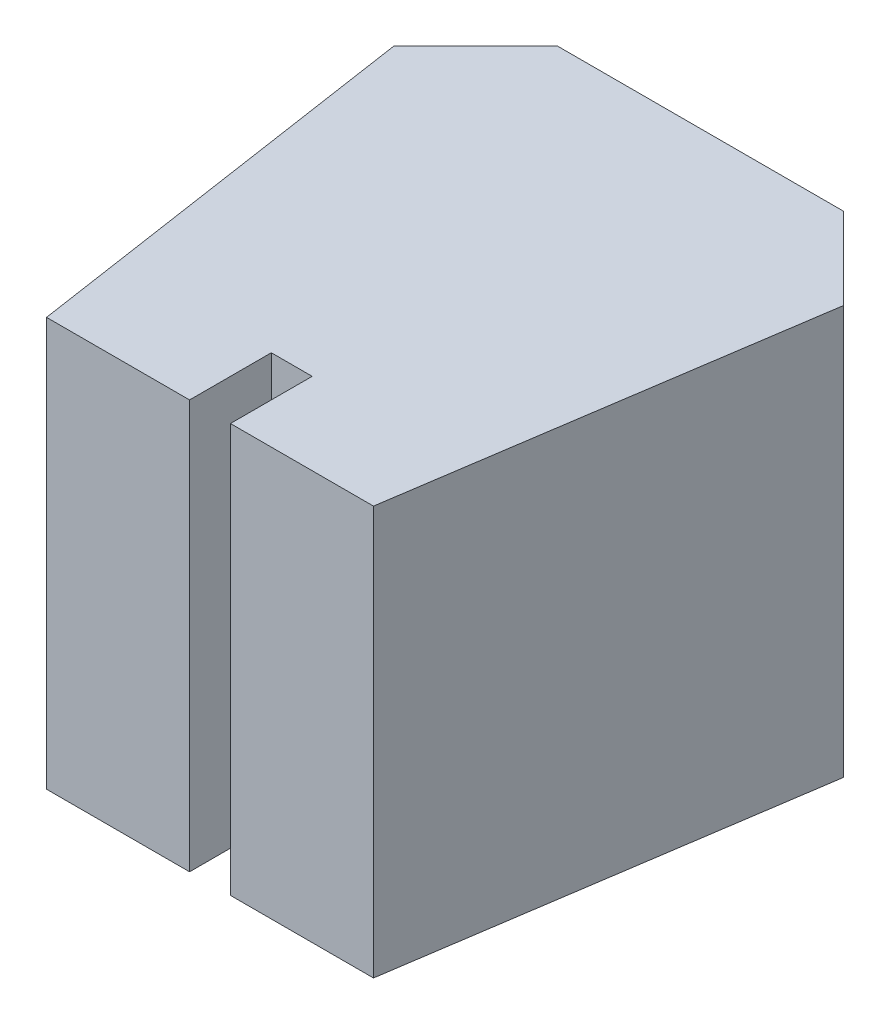
SolidWorks part; units mm, degrees
ref_plane "Front Plane" through (0, 0, 0) normal (0, 0, 1) x (1, 0, 0)
ref_plane "Top Plane" through (0, 0, 0) normal (0, 1, 0) x (1, 0, 0)
ref_plane "Right Plane" through (0, 0, 0) normal (1, 0, 0) x (0, 0, -1)
sketch "Sketch1" plane through (0, 0, -208.1854) normal (0, -1, 0) x (-1, 0, 0)
  line L8 (-175, 91.8146) -> (-275, -8.1854)
  line L9 (-175, 91.8146) -> (175, 91.8146)
  line L10 (-275, 300) -> (-275, -300) construction
  line L13 (-200, -508.1854) -> (200, -508.1854)
  line L14 (275, 300) -> (275, -300) construction
  line L15 (175, 91.8146) -> (275, -8.1854)
  line L16 (-275, -8.1854) -> (-200, -508.1854)
  line L17 (275, -8.1854) -> (200, -508.1854)
  line L19 (-25, -508.1854) -> (25, -508.1854)
  line L20 (-25, -508.1854) -> (-25, -408.1854)
  line L21 (-25, -408.1854) -> (25, -408.1854)
  line L22 (25, -508.1854) -> (25, -408.1854)
  dimension "D1" = 550
  dimension "D2" = 600
  dimension "D3" = 275
  dimension "D4" = 300
  dimension "D5" = 100
  dimension "D6" = 100
  dimension "D7" = 75
  dimension "D8" = 75
  dimension "D9" = 50
  dimension "D10" = 100
  dimension "D11" = 25
  dimension "D12" = 100
  dimension "D13" = 100
  dimension "D14" = 400
  dimension "D15" = 500
extrude "Boss-Extrude1" add sketch "Sketch1" along normal blind 500 contours L13 L22 L21 L20 L16 L8 L9 L15 L17 region at (0, 0, -12.9129)
